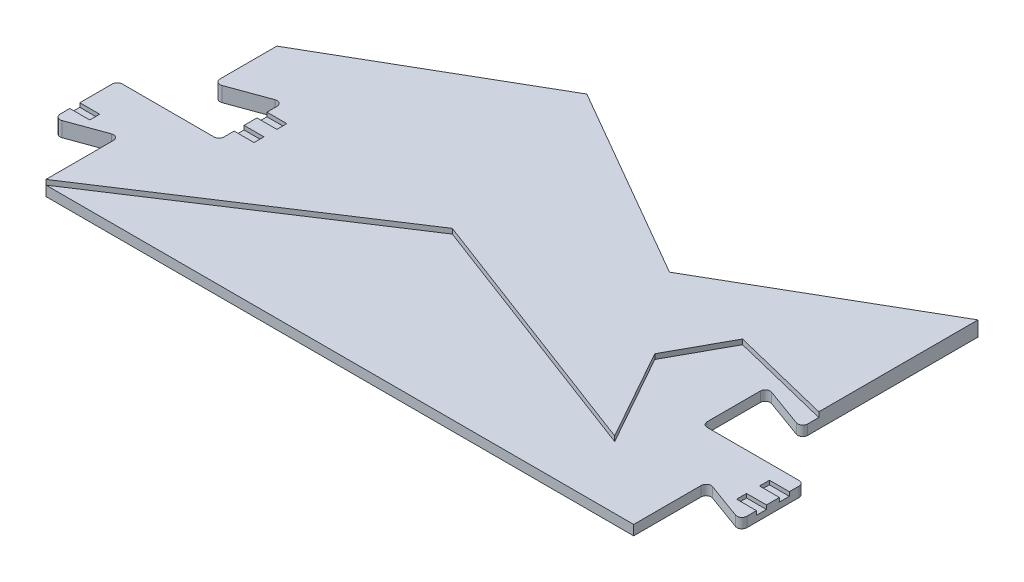
SolidWorks part; units mm, degrees
ref_plane "Přední rovina" through (0, 0, 0) normal (0, 0, 1) x (1, 0, 0)
ref_plane "Horní rovina" through (0, 0, 0) normal (0, 1, 0) x (1, 0, 0)
ref_plane "Pravá rovina" through (0, 0, 0) normal (1, 0, 0) x (0, 0, -1)
sketch "Skica1" plane through (0, 0, 0) normal (0, 1, 0) x (1, 0, 0)
  line L8 (-118.1438, 0) -> (-118.1438, 15)
  line L10 (-118.1438, 15) -> (-128.0938, 11.3785)
  line L11 (-128.0938, 11.3785) -> (-128.0938, 24.2785)
  line L12 (-107.6438, 24.2785) -> (-107.6438, 37.3785)
  line L13 (-107.6438, 37.3785) -> (-118.1432, 33.557)
  line L17 (-118.1432, 33.557) -> (-118.1432, 46.41)
  line L18 (-118.1432, 46.41) -> (-78.6351, 69.22)
  line L19 (-78.6351, 69.22) -> (-39.3176, 46.52)
  line L20 (-118.1438, 15) -> (-118.1438, 56.5658) construction
  line L21 (-107.6438, 24.2785) -> (-128.0938, 24.2785)
  line L22 (-68.7793, 32.3134) -> (-118.1438, 0)
  line L23 (-68.7793, 32.3134) -> (-16.3273, 12.5112)
  line L24 (-16.3273, 12.5112) -> (-26.5931, 30.831)
  line L25 (-26.5931, 30.831) -> (-20.3432, 42.23)
  line L26 (-39.3176, 46.52) -> (0, 69.22)
  line L28 (-118.1438, 0) -> (0, 0)
  line L29 (-20.3432, 42.23) -> (0, 37.22)
  line L30 (0, 0) -> (0, 15)
  line L33 (0, 69.22) -> (0, 0) construction
  line L34 (-10.5, 24.2783) -> (9.9505, 24.2783)
  line L39 (0, 69.22) -> (0, 33.5566)
  line L40 (0, 15) -> (9.9505, 11.3783)
  line L41 (9.9505, 24.2783) -> (9.9505, 11.3783)
  line L42 (0, 33.5566) -> (-10.5, 37.3783)
  line L43 (-10.5, 37.3783) -> (-10.5, 24.2783)
  point P27 (-0.2747, 24.2783)
  dimension "D1" = 45.4
  dimension "D2" = 45.62
  dimension "D3" = 120
  dimension "D4" = 70
  dimension "D5" = 12.9
  dimension "D6" = 13.1
  dimension "D7" = 70
  dimension "D8" = 10.5
  dimension "D9" = 15
  dimension "D10" = 122
  dimension "D11" = 13
  dimension "D12" = 21
  dimension "D13" = 56.0655
  dimension "D14" = 120
  dimension "D15" = 59
  dimension "D16" = 45.4
  dimension "D17" = 120
  dimension "D18" = 118.1438
  dimension "D19" = 104.9
  dimension "D20" = 32.3134
  dimension "D21" = 70
  dimension "D22" = 13.1
  dimension "D23" = 70
  dimension "D24" = 10.5
  dimension "D25" = 15
  dimension "D26" = 12.5112
  dimension "D27" = 69.22
  dimension "D28" = 32
  dimension "D29" = 12.9
  dimension "D30" = 69.22
  dimension "D31" = 9.95
extrude "Přidat vysunutím1" add sketch "Skica1" along normal blind 3 contours L20 L23 L24 L25 L29 L39 L26 L19 L18 L17 L13 L12 L21 | L10 L20 L21 L11 region at (-65.1722, 0, -39.791) region at (-123.3895, 0, -18.6846)
extrude "Přidat vysunutím2" add sketch "Skica1<5>" along normal blind 2 contours L43 L42 L39 L29 L25 L24 L23 L8 L28 L30 L40 L41 L34 region at (-46.7963, 0, -13.9892)
sketch "Skica1<5>" plane through (0, 0, 0) normal (0, 1, 0) x (1, 0, 0) same geometry as "Skica1"
fillet "Zaoblit4" radius 1 12 edges at (0, 1, -33.5566) (-10.5, 1, -24.2783) (-10.5, 1, -37.3783) (0, 1, -15) (9.9505, 1, -11.3783) (9.9505, 1, -24.2783) (-128.0938, 1.5, -11.3785) (-128.0938, 1.5, -24.2785) (-107.6438, 1.5, -24.2785) (-107.6438, 1.5, -37.3785) (-118.1432, 1.5, -33.557) (-118.1438, 1.5, -15)
sketch "Skica2" plane through (0, 3, 0) normal (0, 1, 0) x (1, 0, 0)
  line L1 (-124.0938, 14.7426) -> (-128.0938, 14.7426)
  line L3 (-124.0938, 16.7426) -> (-124.0938, 14.7426)
  line L5 (-128.0938, 16.7426) -> (-124.0938, 16.7426)
  line L10 (-128.0938, 18.0426) -> (-90.5805, 18.0426) construction
  line L11 (-128.0938, 12.8066) -> (-128.0938, 23.2785) construction
  line L12 (-68.7793, 32.3134) -> (-118.1438, 0) construction
  line L21 (-128.0938, 14.7426) -> (-128.0938, 16.7426)
  line L22 (-103.6438, 27.3144) -> (-107.6438, 27.3214)
  line L23 (-103.6438, 29.3144) -> (-103.6438, 27.3144)
  line L25 (-107.6438, 29.3144) -> (-103.6438, 29.3144)
  line L26 (-107.6438, 30.6144) -> (-68.3161, 30.6144) construction
  line L27 (-103.6438, 33.9144) -> (-107.6438, 33.9074)
  line L28 (-103.6438, 31.9144) -> (-103.6438, 33.9144)
  line L29 (-107.6438, 31.9144) -> (-103.6438, 31.9144)
  line L30 (-107.6438, 27.3214) -> (-107.6438, 29.3144)
  line L31 (-107.6438, 33.9074) -> (-107.6438, 31.9144)
  line L32 (-107.6438, 25.2785) -> (-107.6438, 35.9503) construction
  point P16 (-107.6438, 30.6144)
  point P23 (0, 0)
  point P30 (0, 0)
  point P31 (0, 0)
  dimension "D1" = 2
  dimension "D2" = 4
  dimension "D3" = 1.3
  dimension "D4" = 4
  dimension "D5" = 4
  dimension "D6" = 2
  dimension "D7" = 4
  dimension "D8" = 1.3
sketch "Skica3" plane through (0, 2, 0) normal (0, 1, 0) x (1, 0, 0)
  line L0 (9.9505, 18.0424) -> (-19.4268, 18.0424) construction
  line L1 (9.9505, 23.2783) -> (9.9505, 12.8065) construction
  line L2 (-16.3273, 12.5112) -> (-26.5931, 30.831) construction
  line L3 (9.9505, 14.7424) -> (5.9505, 14.7424)
  line L11 (9.9505, 21.3424) -> (5.9505, 21.3424)
  line L12 (5.9505, 21.3424) -> (5.9505, 19.3424)
  line L13 (5.9505, 19.3424) -> (9.9505, 19.3424)
  line L19 (9.9505, 21.3424) -> (9.9505, 19.3424)
  line L20 (5.9505, 14.7424) -> (5.9505, 16.7424)
  line L21 (5.9505, 16.7424) -> (9.9505, 16.7424)
  line L22 (9.9505, 14.7424) -> (9.9505, 16.7424)
  dimension "D4" = 2
  dimension "D5" = 4
  dimension "D6" = 1.3
extrude "Odebrat vysunutím2" cut sketch "Skica2" against normal blind 0.8
extrude "Odebrat vysunutím3" cut sketch "Skica3" against normal blind 0.8
